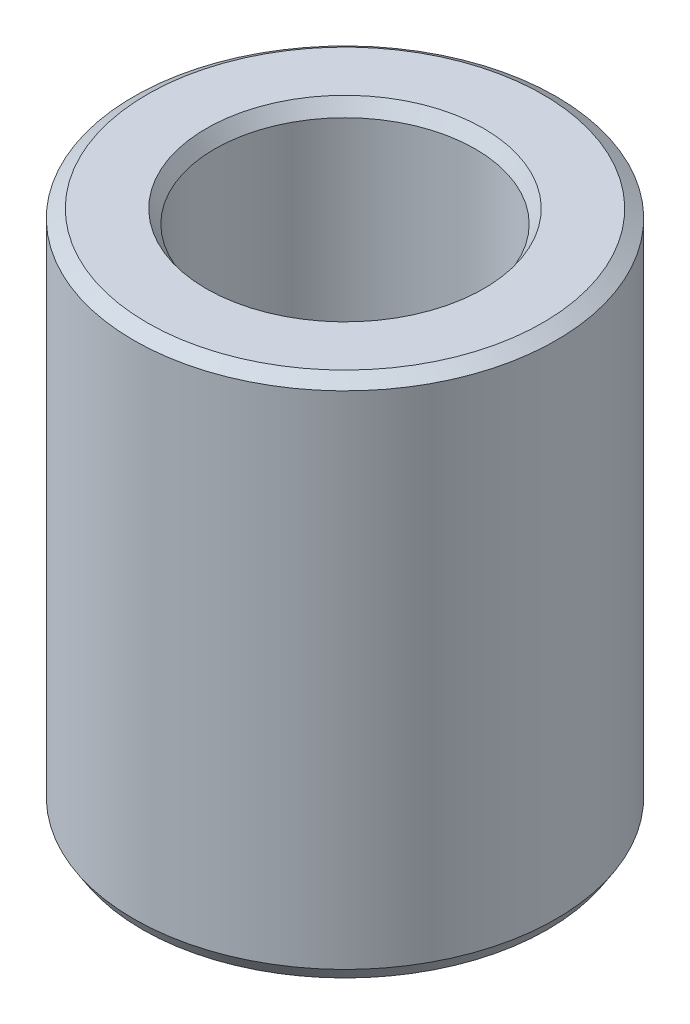
SolidWorks part; units mm, degrees
ref_plane "Front Plane" through (0, 0, 0) normal (0, 0, 1) x (1, 0, 0)
ref_plane "Top Plane" through (0, 0, 0) normal (0, 1, 0) x (1, 0, 0)
ref_plane "Right Plane" through (0, 0, 0) normal (1, 0, 0) x (0, 0, -1)
sketch "Sketch1" plane through (0, 0, 0) normal (0, 1, 0) x (1, 0, 0)
  circle A0 centre (0, 0) radius 32.5
  dimension "SLEEVE_OD" = 65
extrude "Boss-Extrude1" add sketch "Sketch1" along normal blind 80.4752
sketch "Sketch2" plane through (0, 0, 0) normal (0, 1, 0) x (1, 0, 0)
  circle A0 centre (0, 0) radius 20.042
  dimension "BORE_D" = 40.0841
extrude "Cut-Extrude1" cut sketch "Sketch2" along normal through all
chamfer "Chamfer1" distance 1.3113 angle 57.583 4 edges at (0, 80.4752, 20.042) (0, 0, 20.042) (0, 0, 32.5) (0, 80.4752, 32.5) first distance on face at (0, 80.4752, 20.042) first distance on face at (0, 0, 20.042) first distance on face at (0, 80.4752, 32.5)
